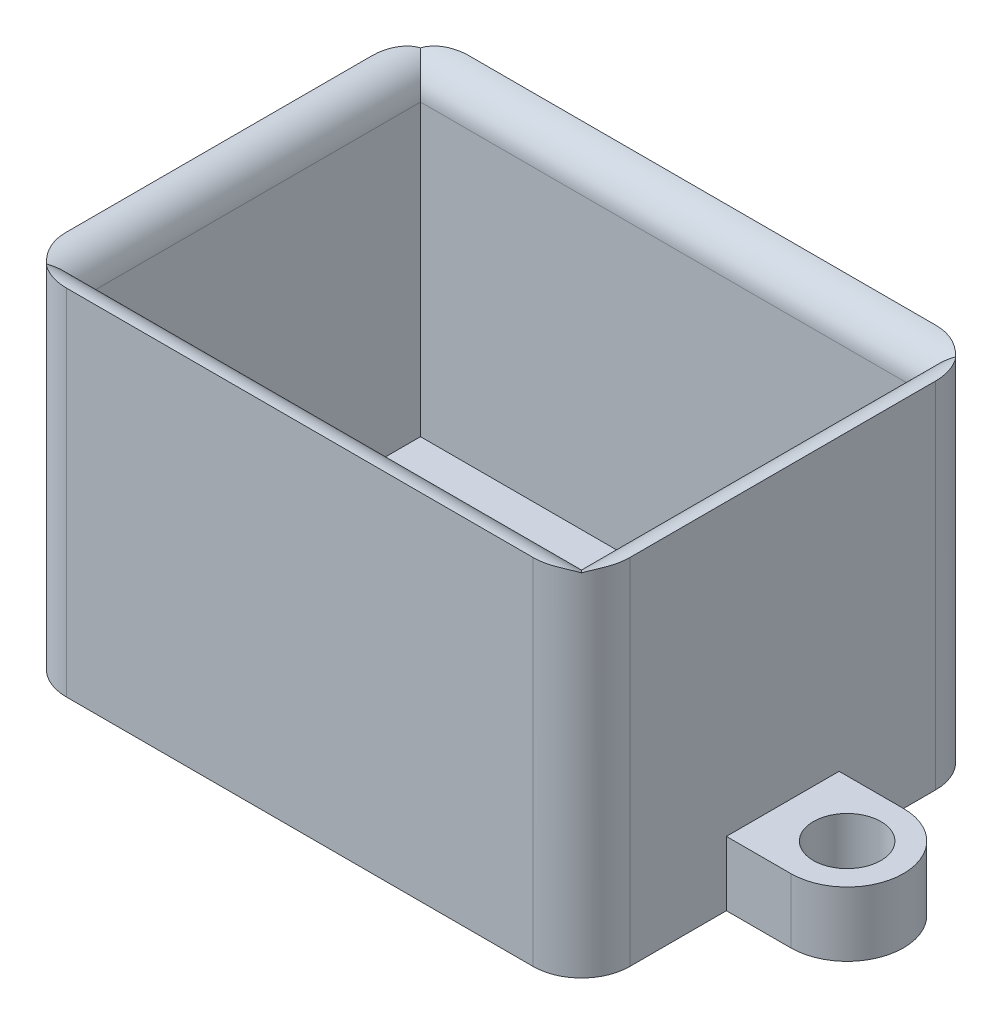
SolidWorks part; units mm, degrees
ref_plane "Front Plane" through (0, 0, 0) normal (0, 0, 1) x (1, 0, 0)
ref_plane "Top Plane" through (0, 0, 0) normal (0, 1, 0) x (1, 0, 0)
ref_plane "Right Plane" through (0, 0, 0) normal (1, 0, 0) x (0, 0, -1)
sketch "Sketch2" plane through (0, 0, 0) normal (0, 1, 0) x (1, 0, 0)
  line L1 (-15.5, 10.5) -> (15.5, 10.5)
  line L2 (-15.5, 10.5) -> (-15.5, -10.5)
  line L3 (-15.5, -10.5) -> (15.5, -10.5)
  line L4 (15.5, 10.5) -> (15.5, -10.5)
  line L5 (-15.5, 10.5) -> (15.5, -10.5) construction
  line L6 (-15.5, -10.5) -> (15.5, 10.5) construction
  line L7 (-17.5, 12.5) -> (17.5, 12.5)
  line L8 (-17.5, 12.5) -> (-17.5, -12.5)
  line L9 (-17.5, -12.5) -> (17.5, -12.5)
  line L10 (17.5, 12.5) -> (17.5, -12.5)
  line L11 (-17.5, 12.5) -> (17.5, -12.5) construction
  line L12 (-17.5, -12.5) -> (17.5, 12.5) construction
  point P0 (0, 0)
  point P6 (0, 0)
  dimension "D1" = 31
  dimension "D2" = 21
  dimension "D3" = 2
  dimension "D4" = 2
extrude "Boss-Extrude1" add sketch "Sketch2" along normal blind 20
sketch "Sketch3" plane through (0, 0, 0) normal (0, -1, 0) x (1, 0, 0)
  line L1 (-17.5, 12.5) -> (17.5, 12.5)
  line L2 (-17.5, 12.5) -> (-17.5, -12.5)
  line L3 (-17.5, -12.5) -> (17.5, -12.5)
  line L4 (17.5, 12.5) -> (17.5, -12.5)
extrude "Boss-Extrude2" add sketch "Sketch3" along normal blind 2
sketch "Sketch4" plane through (0, -2, 0) normal (0, -1, 0) x (1, 0, 0)
  line L0 (0, 12.5) -> (0, -12.5) construction
  line L1 (17.5, 12.5) -> (-17.5, 12.5) construction
  line L2 (-17.5, -12.5) -> (17.5, -12.5) construction
  line L3 (-21.5, 3.5) -> (-17.5, 3.5)
  line L4 (-17.5, 12.5) -> (-17.5, -12.5) construction
  line L5 (-21.5, -3.5) -> (-17.5, -3.5)
  line L6 (-17.5, 3.5) -> (-17.5, -3.5)
  line L7 (0, 0) -> (-17.5, 0) construction
  line L8 (17.5, 3.5) -> (17.5, -3.5)
  line L9 (21.5, -3.5) -> (17.5, -3.5)
  line L10 (21.5, 3.5) -> (17.5, 3.5)
  arc A0 (-21.5, 3.5) -> (-21.5, -3.5) centre (-21.5, 0) ccw
  circle A1 centre (-21.5, 0) radius 2.1
  circle A2 centre (21.5, 0) radius 2.1
  arc A3 (21.5, 3.5) -> (21.5, -3.5) centre (21.5, 0) cw
  dimension "D1" = 3.5
  dimension "D2" = 4.2
  dimension "D3" = 4
extrude "Boss-Extrude3" add sketch "Sketch4" against normal blind 4
fillet "Fillet1" radius 3 4 edges at (17.5, 9, -12.5) (-17.5, 9, -12.5) (17.5, 9, 12.5) (-17.5, 9, 12.5)
fillet "Fillet2" radius 2 4 edges at (15.5, 20, 0) (0, 20, -10.5) (-15.5, 20, 0) (0, 20, 10.5)
